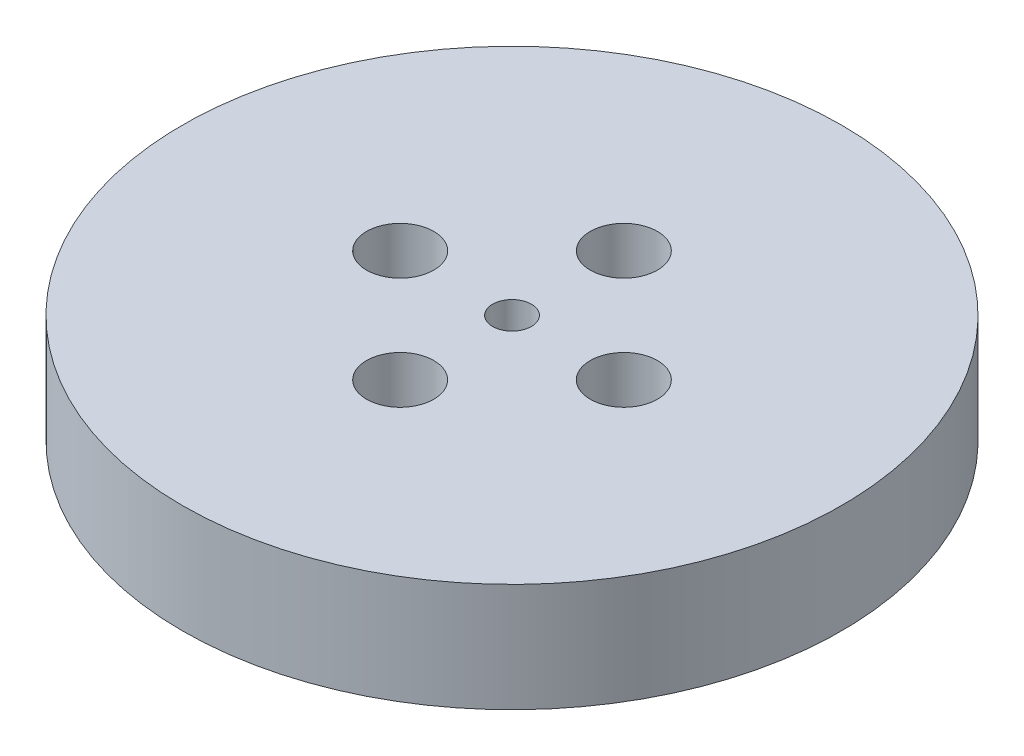
SolidWorks part; units mm, degrees
ref_plane "Front Plane" through (0, 0, 0) normal (0, 0, 1) x (1, 0, 0)
ref_plane "Top Plane" through (0, 0, 0) normal (0, 1, 0) x (1, 0, 0)
ref_plane "Right Plane" through (0, 0, 0) normal (1, 0, 0) x (0, 0, -1)
sketch "Sketch1" plane through (0, 0, 0) normal (0, 1, 0) x (1, 0, 0)
  circle A0 centre (0, 0) radius 85
  dimension "FLANGE_OD" = 170
extrude "Boss-Extrude1" add sketch "Sketch1" along normal blind 28
sketch "Sketch2" plane through (0, 0, 0) normal (0, 1, 0) x (1, 0, 0)
  circle A0 centre (0, 0) radius 5
  dimension "BORE_D" = 10
extrude "Cut-Extrude1" cut sketch "Sketch2" along normal through all
sketch "Sketch3" plane through (0, 28, 0) normal (0, 1, 0) x (1, 0, 0)
  circle A0 centre (0, 0) radius 28.8436 construction
  circle A1 centre (-28.8436, 0) radius 8.6669
  dimension "BOLT_D" = 17.3337
  dimension "BOLT_PCD" = 57.6872
extrude "Cut-Extrude2" cut sketch "Sketch3" against normal blind 18.6695
pattern_circular "CirPattern1" count 4 over 360 about axis through (0, 0, 0) along (0, 1, 0) of "Cut-Extrude2"
